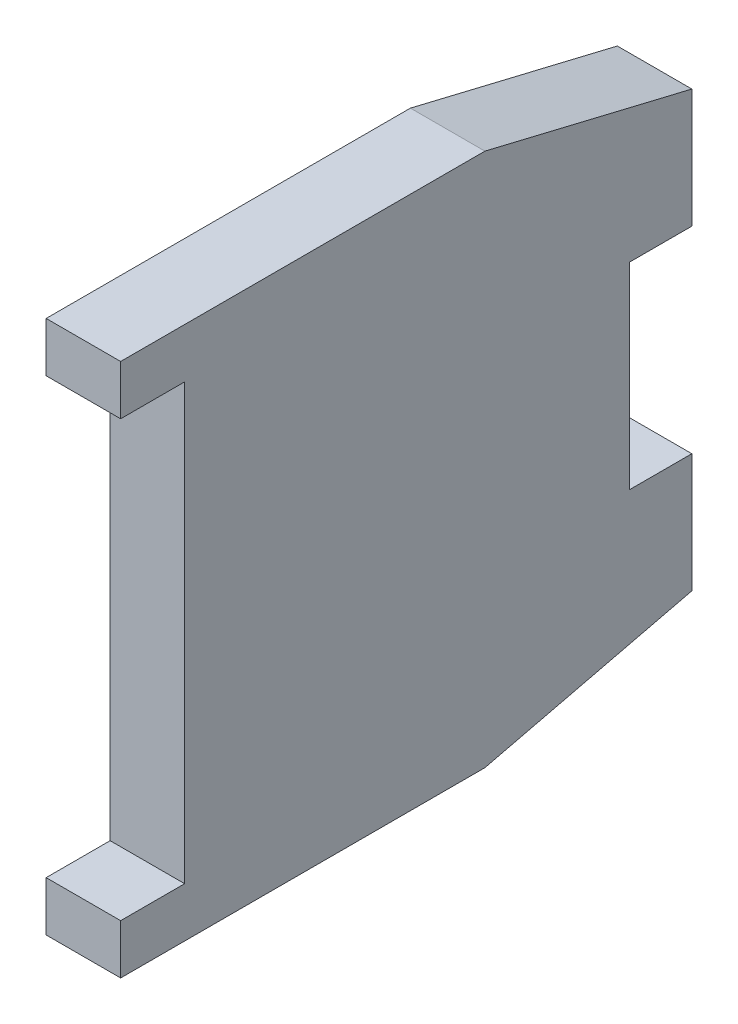
SolidWorks part; units mm, degrees
ref_plane "前视基准面" through (0, 0, 0) normal (0, 0, 1) x (1, 0, 0)
ref_plane "上视基准面" through (0, 0, 0) normal (0, 1, 0) x (1, 0, 0)
ref_plane "右视基准面" through (0, 0, 0) normal (1, 0, 0) x (0, 0, -1)
sketch "草图1" plane through (0, 0, 0) normal (1, 0, 0) x (0, 0, -1)
  line L0 (0, 52.9257) -> (0, -65.8977) construction
  line L1 (-128.0336, 0) -> (98.198, 0) construction
  line L2 (0, 17.5) -> (0, 21.5)
  line L3 (5.1533, 17.5) -> (5.1533, -17.5)
  line L4 (0, 21.5) -> (29.333, 21.5)
  line L5 (29.333, 21.5) -> (46, 17.5)
  line L6 (46, 17.5) -> (46, 7.9341)
  line L7 (0, 17.5) -> (5.1533, 17.5)
  line L8 (46, 7.9341) -> (40.9628, 7.9341)
  line L9 (40.9628, 7.9341) -> (40.9628, -7.9341)
  line L10 (46, -7.9341) -> (40.9628, -7.9341)
  line L11 (0, -17.5) -> (5.1533, -17.5)
  line L12 (46, -17.5) -> (46, -7.9341)
  line L13 (29.333, -21.5) -> (46, -17.5)
  line L14 (0, -21.5) -> (29.333, -21.5)
  line L15 (0, -17.5) -> (0, -21.5)
  point P14 (5.1533, 0)
  point P16 (40.9628, 0)
  point P22 (5.1533, 0)
  dimension "D1" = 46
  dimension "D2" = 43
extrude "凸台-拉伸1" add sketch "草图1" along normal blind 3 and the other way blind 3
